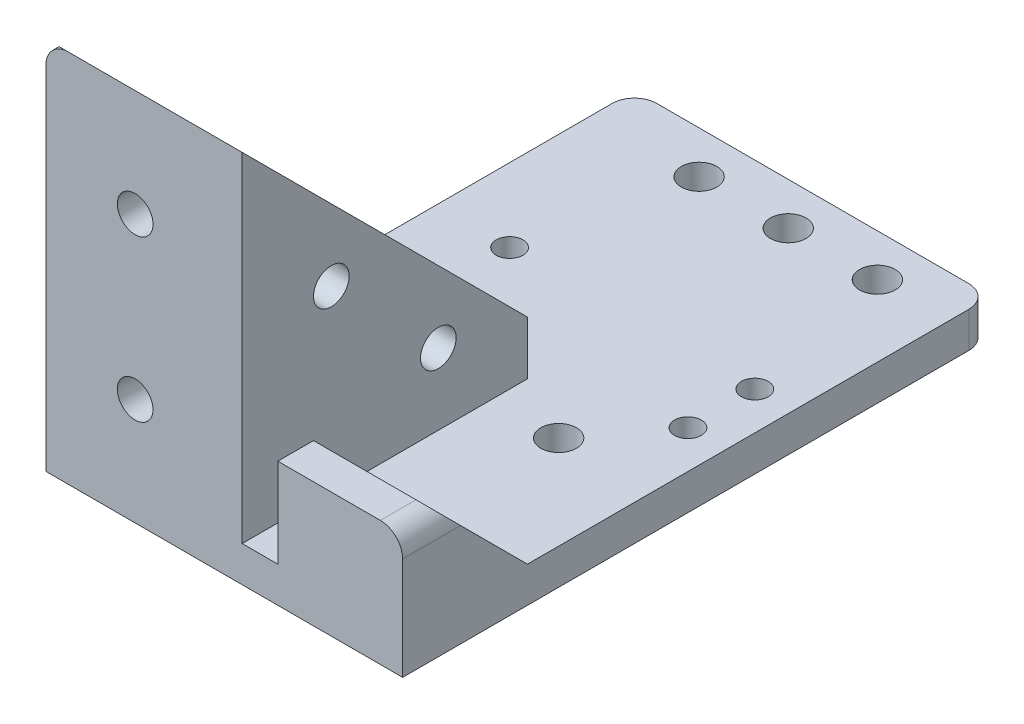
SolidWorks part; units mm, degrees
ref_plane "Front Plane" through (0, 0, 0) normal (0, 0, 1) x (1, 0, 0)
ref_plane "Top Plane" through (0, 0, 0) normal (0, 1, 0) x (1, 0, 0)
ref_plane "Right Plane" through (0, 0, 0) normal (1, 0, 0) x (0, 0, -1)
sketch "Sketch1" plane through (0, 0, 0) normal (0, 1, 0) x (1, 0, 0)
  line L0 (0, 108.3742) -> (0, -10.7395) construction
  line L1 (-51.4374, 0) -> (47.9292, 0) construction
  line L6 (-20, 66) -> (20, 66)
  line L7 (-20, 66) -> (-20, 6)
  line L9 (20, 66) -> (20, 6)
  line L10 (-20, 66) -> (20, 6) construction
  line L11 (-20, 6) -> (20, 66) construction
  line L12 (-20, 0) -> (20, 0)
  line L16 (-20, 6) -> (-20, 0)
  line L17 (20, 6) -> (20, 0)
  line L19 (-19.5962, 6) -> (43.0349, 6) construction
  point P3 (0, 36)
  dimension "D1" = 40
  dimension "D2" = 60
  dimension "D3" = 6
extrude "Boss-Extrude1" add sketch "Sketch1" along normal blind 4
sketch "Sketch2" plane through (0, 4, 0) normal (0, 1, 0) x (1, 0, 0)
  line L0 (-8.0039, 61.25) -> (11.9961, 61.25) construction
  line L1 (1.9961, -14.7291) -> (1.9961, 58.7438) construction
  line L2 (-11.7539, 43.75) -> (15.7461, 43.75) construction
  line L3 (-11.7539, 43.75) -> (-11.7539, 36.25) construction
  line L4 (-11.7539, 36.25) -> (15.7461, 36.25) construction
  line L5 (15.7461, 43.75) -> (15.7461, 36.25) construction
  line L6 (-11.7539, 43.75) -> (15.7461, 36.25) construction
  line L7 (-11.7539, 36.25) -> (15.7461, 43.75) construction
  line L8 (-5.5039, 8) -> (9.4961, 8) construction
  line L9 (-5.5039, 8) -> (-5.5039, 28) construction
  line L10 (-5.5039, 28) -> (9.4961, 28) construction
  line L11 (9.4961, 8) -> (9.4961, 28) construction
  line L12 (-5.5039, 8) -> (9.4961, 28) construction
  line L13 (-5.5039, 28) -> (9.4961, 8) construction
  line L16 (20, 66) -> (-20, 66) construction
  circle A0 centre (-8.0039, 61.25) radius 2
  circle A1 centre (1.9961, 61.25) radius 2
  circle A2 centre (11.9961, 61.25) radius 2
  circle A3 centre (-5.5039, 8) radius 2
  circle A4 centre (-5.5039, 28) radius 2
  circle A5 centre (9.4961, 28) radius 2
  circle A6 centre (9.4961, 8) radius 2
  circle A7 centre (15.7461, 36.25) radius 1.5
  circle A8 centre (15.7461, 43.75) radius 1.5
  circle A9 centre (-11.7539, 43.75) radius 1.5
  circle A10 centre (-11.7539, 36.25) radius 1.5
  point P2 (1.9961, 40)
  point P12 (1.9961, 18)
  point P20 (1.9961, 61.25)
  dimension "D10" = 4
  dimension "D11" = 4
  dimension "D12" = 3
  dimension "D1" = 20
  dimension "D2" = 15
  dimension "D3" = 48
  dimension "D4" = 7.5
  dimension "D5" = 27.5
  dimension "D6" = 26
  dimension "D7" = 4.75
  dimension "D8" = 20
  dimension "D9" = 10
  dimension "D13" = 1.9961
extrude "Cut-Extrude1" cut sketch "Sketch2" against normal through all
ref_plane "Plane1" through (2, 0, 0) normal (1, 0, 0) x (0, 0, -1)
sketch "Sketch5" plane through (2, 0, 0) normal (1, 0, 0) x (0, 0, -1)
  line L0 (0, 4) -> (0, 38)
  line L1 (0, 38) -> (4, 38)
  line L2 (4, 38) -> (32, 10)
  line L3 (32, 10) -> (32, 4)
  line L4 (0, 4) -> (66, 4) construction
  line L5 (32, 4) -> (0, 4)
  dimension "D1" = 34
  dimension "D2" = 4
  dimension "D3" = 6
  dimension "D4" = 45
extrude "Boss-Extrude5" add sketch "Sketch5" against normal blind 4
sketch "Sketch6" plane through (0, 0, 0) normal (0, 0, 1) x (1, 0, 0)
  line L0 (-2, 38) -> (-20, 38)
  line L1 (-2, 38) -> (2, 38) construction
  line L2 (-2, 38) -> (-2, 4) construction
  line L3 (-20, 38) -> (-20, 4)
  line L4 (-20, 4) -> (-2, 4)
  line L5 (-2, 4) -> (-2, 38)
extrude "Boss-Extrude6" add sketch "Sketch6" against normal blind 4
sketch "Sketch7" plane through (0, 0, 0) normal (0, 0, 1) x (1, 0, 0)
  line L0 (6, 4) -> (6, 14)
  line L1 (2, 4) -> (20, 4) construction
  line L2 (6, 14) -> (20, 14)
  line L4 (2, 38) -> (2, 4) construction
  line L5 (6, 4) -> (20, 4)
  line L6 (20, 4) -> (20, 0) construction
  line L7 (20, 4) -> (20, 14)
  dimension "D1" = 4
  dimension "D2" = 10
extrude "Boss-Extrude7" add sketch "Sketch7" against normal blind 4
sketch "Sketch8" plane through (-2, 0, 0) normal (-1, 0, 0) x (0, 0, 1)
  line L0 (-32, 12) -> (-10, 12) construction
  line L1 (-10, 32) -> (-10, 12) construction
  line L2 (-4, 4) -> (-32, 4) construction
  line L3 (0, 38) -> (0, 0) construction
  circle A1 centre (-10, 24) radius 2
  circle A2 centre (-22, 12) radius 2
  dimension "D3" = 4
  dimension "D1" = 12
  dimension "D2" = 12
  dimension "D4" = 10
  dimension "D5" = 8
  dimension "D6" = 10
extrude "Cut-Extrude2" cut sketch "Sketch8" against normal through all
sketch "Sketch9" plane through (0, 0, -4) normal (0, 0, -1) x (-1, 0, 0)
  line L0 (10, 4.695) -> (10, 30.9324) construction
  line L1 (20, 38) -> (20, 4) construction
  line L2 (-20, 4) -> (20, 4) construction
  circle A0 centre (10, 12) radius 2
  circle A1 centre (10, 30) radius 2
  dimension "D4" = 4
  dimension "D1" = 10
  dimension "D2" = 18
  dimension "D3" = 8
extrude "Cut-Extrude3" cut sketch "Sketch9" against normal blind 4
fillet "Fillet1" [suppressed] radius 4
sketch "Sketch10" plane through (2, 0, 0) normal (1, 0, 0) x (0, 0, -1)
  line L0 (4, 38) -> (0, 42)
  line L1 (0, 42) -> (0, 38)
  line L2 (0, 38) -> (4, 38)
extrude "Boss-Extrude8" add sketch "Sketch10" against normal up to surface (22 mm away) up to face at (-20, 14, -23.3333)
sketch "Sketch13" plane through (20, 0, 0) normal (1, 0, 0) x (0, 0, -1)
  line L0 (4, 14) -> (14, 4)
  line L1 (4, 4) -> (4, 14) construction
  line L2 (4, 4) -> (66, 4) construction
  line L3 (4, 14) -> (4, 4)
  line L4 (4, 4) -> (14, 4)
  line L5 (4, 14) -> (0, 14) construction
  point P6 (4, 14)
  dimension "D1" = 45
extrude "Boss-Extrude9" add sketch "Sketch13" against normal blind 4
sketch "Sketch14" plane through (-20, 0, 0) normal (-1, 0, 0) x (0, 0, 1)
  line L0 (0, 42) -> (-32, 10)
  line L1 (-32, 0) -> (-32, 10)
  line L2 (0, 42) -> (0, 0) construction
  line L3 (-32, 0) -> (0, 0)
  line L4 (0, 0) -> (0, 42)
  point P3 (-32.3055, 0)
  dimension "D1" = 45
  dimension "D2" = 32
extrude "Boss-Extrude10" add sketch "Sketch14" against normal blind 4
sketch "Sketch16" plane through (0, 0, 0) normal (0, 0, 1) x (1, 0, 0)
  line L0 (-20, 42) -> (-20, 0) construction
  line L1 (-20, 42) -> (2, 42) construction
  line L2 (-20, 39.5668) -> (-20, 42)
  line L3 (-20, 42) -> (-17.4086, 42)
  arc A0 (-20, 39.5668) -> (-17.4086, 42) centre (-17.5008, 39.5017) cw
  line M5 (-20, 42) -> (-20, 0)
  dimension "D1" = 2.5
extrude "Cut-Extrude5" cut sketch "Sketch16" against normal blind 4 contours A0 L3 M5 region at (-19.4436, 41.4426, 0)
fillet "Fillet7" radius 2.5 2 edges at (-20, 2, -66) (20, 2, -66)
fillet "Fillet8" radius 2.5 1 edges at (20, 14, -2)
